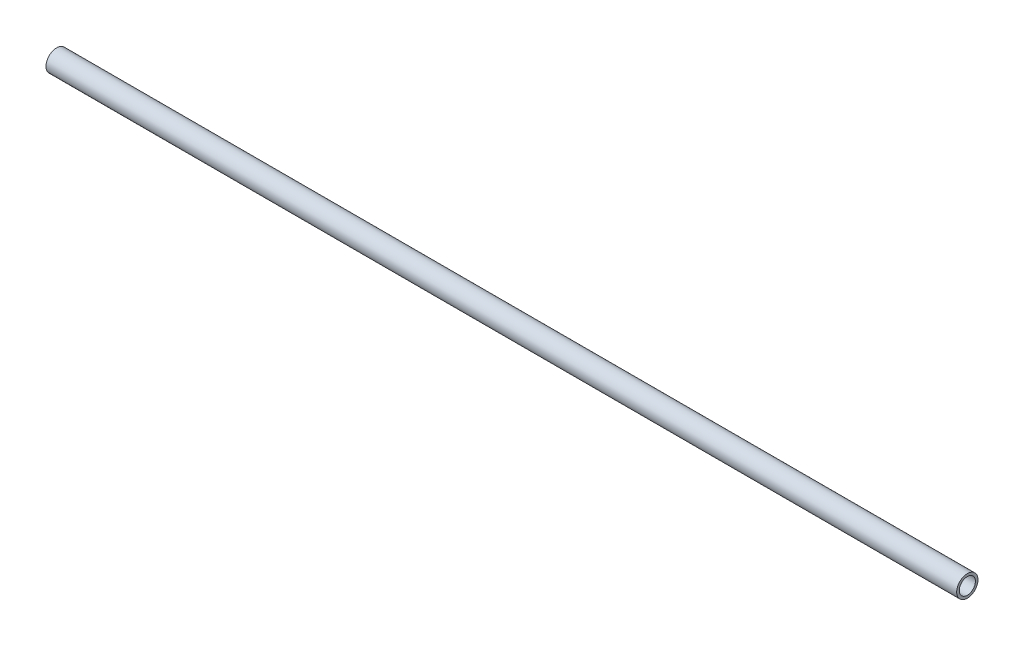
SolidWorks part; units mm, degrees
ref_plane "Front Plane" through (0, 0, 0) normal (0, 0, 1) x (1, 0, 0)
ref_plane "Top Plane" through (0, 0, 0) normal (0, 1, 0) x (1, 0, 0)
ref_plane "Right Plane" through (0, 0, 0) normal (1, 0, 0) x (0, 0, -1)
ref_axis "Axis1" through (-4.5, 0, 0) along (1, 0, 0)
sketch "Sketch1" plane through (0, 0, 0) normal (1, 0, 0) x (0, 0, -1)
  circle A0 centre (0, 0) radius 0.8001
  circle A1 centre (0, 0) radius 1.0541
  dimension "D1" = 1.6002
  dimension "D2" = 2.1082
extrude "Boss-Extrude1" add sketch "Sketch1" along normal blind 90
sketch "Sketch2" plane through (0, 0, 0) normal (-1, 0, 0) x (0, 0, 1)
  line L0 (0, 0) -> (0, 0.6106) construction
  line L2 (-0.304, 0.6106) -> (-0.304, 1.0992)
  line L3 (-0.304, 1.0992) -> (0.304, 1.0992)
  line L4 (0.304, 1.0992) -> (0.304, 0.6106)
  arc A0 (-0.304, 0.6106) -> (0.304, 0.6106) centre (0, 0.6106) ccw
  dimension "D1" = 0.608
extrude "Cut-Extrude1" [suppressed] cut sketch "Sketch2" against normal blind 1
sketch "Sketch3" plane through (0, 0, 0) normal (0, 0, 1) x (1, 0, 0)
  circle A0 centre (0.7986, 0) radius 0.3969
  dimension "D1" = 0.7937
extrude "Cut-Extrude2" cut sketch "Sketch3" against normal blind 10
equation "\"Do\"=8.5mm"
equation "\"Lo\"=10"
equation "\"screw_diam\"= 3.5mm"
equation "\"wheel_Do\"=12.5mm"
equation "\"wheel_thickness\"=4mm"
equation "\"Collet_diameter\"=4.3"
equation "\"clearance\"= 0.5mm"
equation "\"handle_body_width\"= 10mm"
equation "\"finger_diameter\"=35"
equation "\"collet_lid_diameter\"=10"
equation "\"screw_cap_diam\"=5.15"
equation "\"handle_thickness\"=12.5mm"
equation "\"post_hole_diam\"=2"
equation "\"roll_rod_diam\"= 6.5 "
equation "\"roll_rod_length\"=6.6"
equation "\"disc_diam\"=5"
equation "\"disc_width\"=1.5"
equation "\"arm_width\"=5"
equation "\"arm_thickness\"=4.5"
equation "\"wheel_total_diam\"=30"
equation "\"spring_diam\"=4.1"
equation "\"collet_length\"= 18.75mm"
equation "\"tip_length\"= 40mm"
equation "\"cable_tube_OD\"=0.508"
equation "\"D1@Sketch2\"=\"cable_tube_OD\"+0.1"
